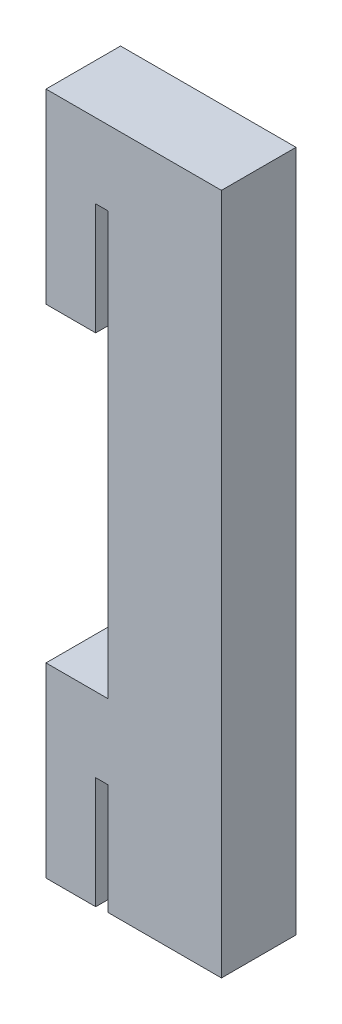
SolidWorks part; units mm, degrees
ref_plane "Plan de face" through (0, 0, 0) normal (0, 0, 1) x (1, 0, 0)
ref_plane "Plan de dessus" through (0, 0, 0) normal (0, 1, 0) x (1, 0, 0)
ref_plane "Plan de droite" through (0, 0, 0) normal (1, 0, 0) x (0, 0, -1)
sketch "Esquisse1" plane through (0, 0, 0) normal (0, 0, 1) x (1, 0, 0)
  line L0 (0, 0) -> (0, 9)
  line L1 (0, 9) -> (1, 9)
  line L4 (1, 0.0964) -> (10.1219, 0.0964)
  line L5 (10.1219, 0.0964) -> (10.1219, 55)
  line L8 (10.1219, 55) -> (-4, 55)
  line L9 (1, 49) -> (0, 49)
  line L10 (0, 0) -> (-4, 0)
  line L11 (-4, 0) -> (-4, 15)
  line L12 (-4, 15) -> (1, 15)
  line L13 (1, 15) -> (1, 49)
  line L14 (0, 49) -> (0, 40)
  line L15 (0, 40) -> (-4, 40)
  line L16 (-4, 40) -> (-4, 55)
  line L17 (1, 9) -> (1, 0.0964)
  point P11 (0.5, 9)
  dimension "D1" = 40
  dimension "D2" = 1
  dimension "D3" = 1
  dimension "D4" = 15
  dimension "D5" = 15
  dimension "D6" = 4
  dimension "D7" = 4
  dimension "D8" = 6
  dimension "D9" = 6
extrude "Boss.-Extru.1" add sketch "Esquisse1" along normal blind 6
